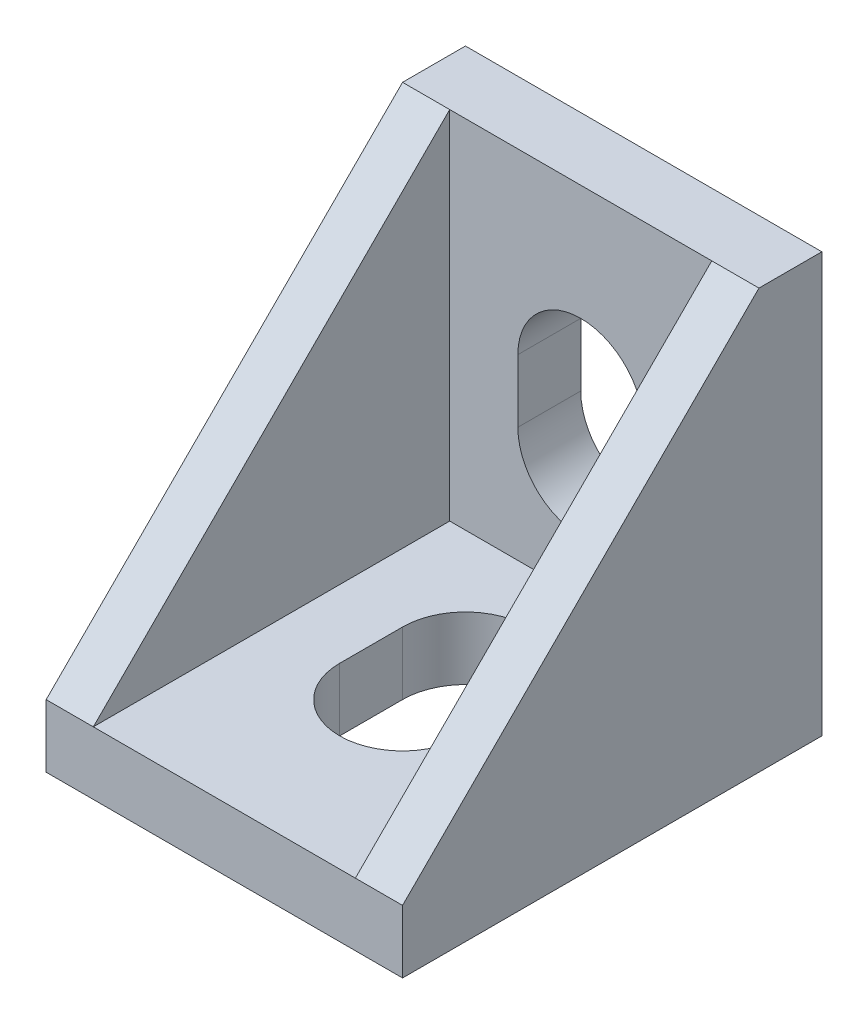
SolidWorks part; units mm, degrees
other "Sunlight"
material "6063-O, Extruded Rod (SS)"
ref_plane "Front Plane" through (0, 0, 0) normal (0, 0, 1) x (1, 0, 0)
ref_plane "Top Plane" through (0, 0, 0) normal (0, 1, 0) x (1, 0, 0)
ref_plane "Right Plane" through (0, 0, 0) normal (1, 0, 0) x (0, 0, -1)
sketch "Sketch4" plane through (0, 0, 0) normal (1, 0, 0) x (0, 0, -1)
  line L0 (7, 10) -> (-10, -7)
  line L1 (7, 10) -> (10, 10)
  line L2 (-10, -7) -> (-10, -10)
  line L3 (-10, -10) -> (10, -10)
  line L4 (10, 10) -> (10, -10)
  line L5 (10, 10) -> (-10, -10) construction
  point P0 (0, 0)
  dimension "D1" = 20
  dimension "D2" = 20
  dimension "D3" = 3
  dimension "D4" = 3
  dimension "D5" = 0
extrude "Boss-Extrude3" add sketch "Sketch4" along normal blind 17
shell "Shell4" thickness 2.25 removed face at (8.5, 10, -8.5) removed face at (8.5, -8.5, 10) removed face at (8.5, 1.5, 1.5)
sketch "Sketch5" plane through (0, 0, -10) normal (0, 0, -1) x (-1, 0, 0)
  line L0 (-11.5, 1.5) -> (-11.5, -1.5)
  line L1 (-5.5, 1.5) -> (-5.5, -1.5)
  line L2 (-8.5, 4.5) -> (-8.5, -4.5) construction
  line L3 (-17, 10) -> (0, 10)
  line L6 (-8.5, 10) -> (-8.5, -10) construction
  line L7 (-17, -10) -> (0, -10) construction
  line L8 (-11.5, 0) -> (-5.5, 0) construction
  line L9 (-17, 0) -> (0, 0) construction
  line L10 (-17, -10) -> (-17, 10) construction
  arc A0 (-5.5, 1.5) -> (-11.5, 1.5) centre (-8.5, 1.5) ccw
  arc A1 (-11.5, -1.5) -> (-5.5, -1.5) centre (-8.5, -1.5) ccw
  point P3 (-8.5, 4.5)
  point P8 (-8.5, -4.5)
  point P19 (-17, 10)
  point P21 (-8.5, 10)
  dimension "D1" = 6
  dimension "D2" = 9
  dimension "D3" = 0
  dimension "D4" = 0
extrude "Cut-Extrude1" cut sketch "Sketch5" against normal through all contours L1 A1 L0 A0
sketch "Sketch8" plane through (0, -10, 0) normal (0, -1, 0) x (-1, 0, 0)
  line L0 (-11.5, 1.5) -> (-11.5, -1.5)
  line L1 (-5.5, 1.5) -> (-5.5, -1.5)
  line L2 (-8.5, 4.5) -> (-8.5, -4.5) construction
  line L3 (-8.5, 10) -> (-8.5, -10) construction
  line L4 (-17, 10) -> (0, 10) construction
  line L5 (-17, -10) -> (0, -10) construction
  line L6 (-17, 0) -> (0, 0) construction
  line L8 (-11.5, 0) -> (-5.5, 0) construction
  line L9 (-17, -10) -> (-17, 10) construction
  line L11 (0, -10) -> (0, 10) construction
  arc A0 (-5.5, 1.5) -> (-11.5, 1.5) centre (-8.5, 1.5) ccw
  arc A1 (-11.5, -1.5) -> (-5.5, -1.5) centre (-8.5, -1.5) ccw
  point P3 (-8.5, 4.5)
  point P8 (-8.5, -4.5)
  dimension "D1" = 6
  dimension "D2" = 9
  dimension "D3" = 0
  dimension "D4" = 0
extrude "Cut-Extrude2" cut sketch "Sketch8" against normal through all
sketch "Sketch9" plane through (0, 0, -10) normal (0, 0, -1) x (-1, 0, 0)
  line L0 (-9.525, 8.125) -> (-7.475, 8.125)
  line L1 (-9.525, 6.375) -> (-7.475, 6.375)
  line L2 (-8.5, 10) -> (-8.5, -10) construction
  line L3 (-17, 10) -> (0, 10) construction
  line L4 (-17, -10) -> (0, -10) construction
  line L5 (-8.5, 8.125) -> (-8.5, 6.375) construction
  line L6 (-17, 4.5) -> (0, 4.5) construction
  line L7 (-8.5, 4.5) -> (0, 4.5) construction
  line L9 (0, 10) -> (0, 4.5) construction
  line L10 (0, -10) -> (0, 10) construction
  line L11 (0, 7.25) -> (-17, 7.25) construction
  line L12 (-17, -10) -> (-17, 10) construction
  line L13 (-10.4, 7.25) -> (-6.6, 7.25) construction
  arc A0 (-7.475, 6.375) -> (-7.475, 8.125) centre (-7.475, 7.25) ccw
  arc A1 (-9.525, 8.125) -> (-9.525, 6.375) centre (-9.525, 7.25) ccw
  arc A2 (-5.5, 1.5) -> (-11.5, 1.5) centre (-8.5, 1.5) ccw construction
  point P1 (-10.4, 7.25)
  point P3 (-6.6, 7.25)
  point P24 (-8.5, 4.5)
  point P25 (-8.5, 4.5)
  dimension "D1" = 1.75
  dimension "D2" = 3.8
  dimension "D3" = 0
  dimension "D4" = 0
  dimension "D5" = 0
  dimension "D6" = 0
extrude "Boss-Extrude4" add sketch "Sketch9" along normal blind 1
sketch "Sketch10" plane through (0, 0, -10) normal (0, 0, -1) x (-1, 0, 0)
  line L0 (-9.525, -6.375) -> (-7.475, -6.375)
  line L1 (-9.525, -8.125) -> (-7.475, -8.125)
  line L2 (-8.5, 10) -> (-8.5, -10) construction
  line L5 (-8.5, -6.375) -> (-8.5, -8.125) construction
  line L6 (-17, 10) -> (0, 10) construction
  line L7 (-17, -10) -> (0, -10) construction
  line L8 (-8.5, -4.5) -> (0, -4.5) construction
  line L11 (0, -10) -> (0, 10) construction
  line L13 (-10.4, -7.25) -> (-6.6, -7.25) construction
  line L14 (0, -4.5) -> (0, -10) construction
  line L15 (0, -7.25) -> (-17, -7.25) construction
  line L16 (-17, -10) -> (-17, 10) construction
  arc A0 (-7.475, -8.125) -> (-7.475, -6.375) centre (-7.475, -7.25) ccw
  arc A1 (-9.525, -6.375) -> (-9.525, -8.125) centre (-9.525, -7.25) ccw
  arc A3 (-11.5, -1.5) -> (-5.5, -1.5) centre (-8.5, -1.5) ccw construction
  point P1 (-10.4, -7.25)
  point P3 (-6.6, -7.25)
  point P24 (-8.3945, -3.5679)
  point P25 (-8.3945, -3.5679)
  dimension "D1" = 1.75
  dimension "D2" = 3.8
  dimension "D3" = 0
  dimension "D4" = 0
extrude "Boss-Extrude5" add sketch "Sketch10" along normal blind 1
sketch "Sketch12" plane through (-0.8438, -10, -7.7593) normal (0, -1, 0) x (-1, 0, 0)
  line L0 (-10.3688, 0.3657) -> (-8.3188, 0.3657)
  line L1 (-10.3688, -1.3843) -> (-8.3188, -1.3843)
  line L2 (-9.3438, 10) -> (-9.3438, -10) construction
  line L5 (-9.3438, 0.3657) -> (-9.3438, -1.3843) construction
  line L6 (-9.3438, -3.2593) -> (-0.8438, -3.2593) construction
  line L7 (-0.8438, -17.7593) -> (-0.8438, 2.2407) construction
  line L8 (-0.8438, -3.2593) -> (-0.8438, 2.2407) construction
  line L9 (-0.8438, -0.5093) -> (-17.8438, -0.5093) construction
  line L11 (-17.8438, -17.7593) -> (-17.8438, 2.2407) construction
  line L13 (-11.2438, -0.5093) -> (-7.4438, -0.5093) construction
  line L14 (-9.3438, 2.2407) -> (-9.3438, -3.2593) construction
  line L15 (-10.3688, 2.2407) -> (-8.3188, 2.2407) construction
  arc A0 (-8.3188, -1.3843) -> (-8.3188, 0.3657) centre (-8.3188, -0.5093) ccw
  arc A1 (-10.3688, 0.3657) -> (-10.3688, -1.3843) centre (-10.3688, -0.5093) ccw
  arc A3 (-6.3438, -6.2593) -> (-12.3438, -6.2593) centre (-9.3438, -6.2593) ccw construction
  point P1 (-11.2438, -0.5093)
  point P3 (-7.4438, -0.5093)
  point P24 (-8.5, 4.5)
  point P25 (-8.5, 4.5)
  dimension "D1" = 1.75
  dimension "D2" = 3.8
  dimension "D3" = 0
  dimension "D4" = 0
  dimension "D5" = 0
extrude "Boss-Extrude6" add sketch "Sketch12" along normal blind 1
sketch "Sketch14" plane through (-0.8438, -10, -7.7593) normal (0, -1, 0) x (-1, 0, 0)
  line L0 (-10.3688, -14.1343) -> (-8.3188, -14.1343)
  line L1 (-10.3688, -15.8843) -> (-8.3188, -15.8843)
  line L2 (-9.3438, 2.2407) -> (-9.3438, -17.7593) construction
  line L3 (-10.3688, 2.2407) -> (-8.3188, 2.2407) construction
  line L4 (-17.8438, -17.7593) -> (-0.8438, -17.7593) construction
  line L5 (-9.3438, -14.1343) -> (-9.3438, -15.8843) construction
  line L8 (-9.3438, -12.2593) -> (-0.8438, -12.2593) construction
  line L9 (-0.8438, -17.7593) -> (-0.8438, 2.2407) construction
  line L10 (-0.8438, -12.2593) -> (-0.8438, -17.7593) construction
  line L12 (-0.8438, -15.0093) -> (-17.8438, -15.0093) construction
  line L13 (-11.2438, -15.0093) -> (-7.4438, -15.0093) construction
  line L14 (-17.8438, -17.7593) -> (-17.8438, 2.2407) construction
  arc A0 (-8.3188, -15.8843) -> (-8.3188, -14.1343) centre (-8.3188, -15.0093) ccw
  arc A1 (-10.3688, -14.1343) -> (-10.3688, -15.8843) centre (-10.3688, -15.0093) ccw
  arc A2 (-12.3438, -9.2593) -> (-6.3438, -9.2593) centre (-9.3438, -9.2593) ccw construction
  point P1 (-11.2438, -15.0093)
  point P3 (-7.4438, -15.0093)
  point P24 (-8.3945, -3.5679)
  point P25 (-8.3945, -3.5679)
  dimension "D1" = 1.75
  dimension "D2" = 3.8
  dimension "D3" = 0
  dimension "D4" = 0
extrude "Boss-Extrude7" add sketch "Sketch14" along normal blind 1
